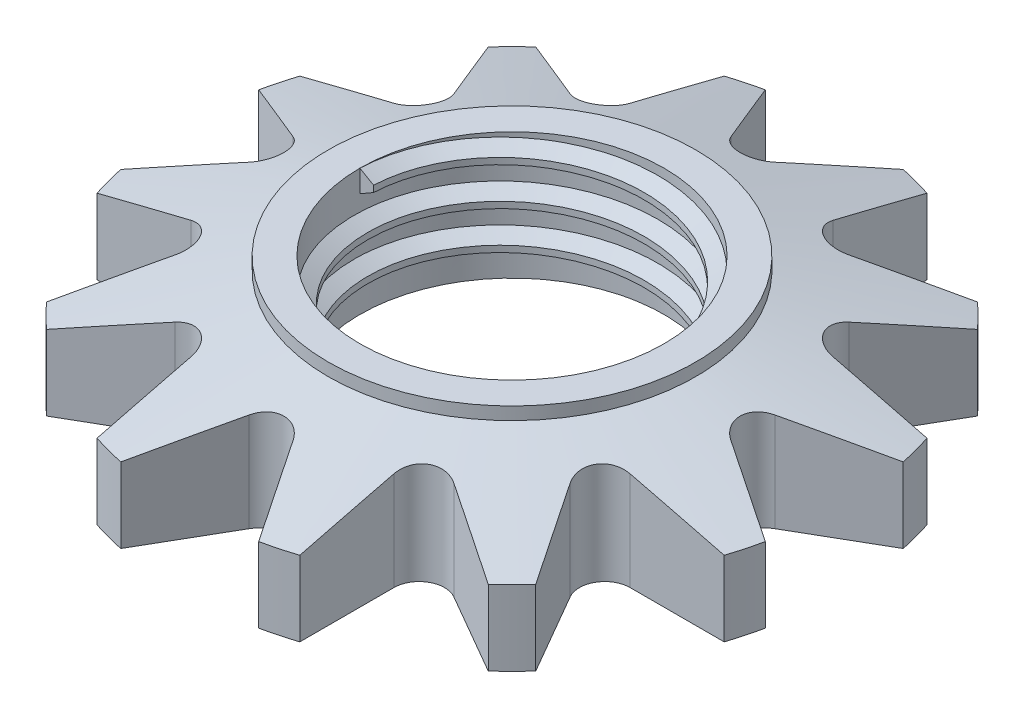
SolidWorks part; units mm, degrees
ref_plane "Front Plane" through (0, 0, 0) normal (0, 0, 1) x (1, 0, 0)
ref_plane "Top Plane" through (0, 0, 0) normal (0, 1, 0) x (1, 0, 0)
ref_plane "Right Plane" through (0, 0, 0) normal (1, 0, 0) x (0, 0, -1)
sketch "Sketch1" plane through (0, 0, 0) normal (0, 1, 0) x (1, 0, 0)
  circle A0 centre (0, 0) radius 26
  circle A1 centre (0, 0) radius 12
  dimension "D1" = 52
  dimension "D2" = 24
extrude "Boss-Extrude1" add sketch "Sketch1" along normal blind 9
sketch "Sketch2" plane through (0, 9, 0) normal (0, 1, 0) x (1, 0, 0)
  circle A0 centre (0, 0) radius 14.5
  circle A1 centre (0, 0) radius 12 construction
  circle A2 centre (0, 0) radius 12
  dimension "D1" = 29
extrude "Boss-Extrude2" add sketch "Sketch2" along normal blind 1
sketch "Sketch3" plane through (0, 9, 0) normal (0, 1, 0) x (1, 0, 0)
  line L0 (0, 26) -> (0, 0) construction
  line L1 (0, 0) -> (-26, 0) construction
  line L2 (-5.4411, 25.4243) -> (-1.7321, 19)
  line L3 (5.4411, 25.4243) -> (1.7321, 19)
  line L4 (8, 24.7386) -> (8, 17.3205)
  line L5 (17.4243, 19.2975) -> (11, 15.5885)
  line L6 (19.2975, 17.4243) -> (15.5885, 11)
  line L7 (24.7386, 8) -> (17.3205, 8)
  line L8 (25.4243, 5.4411) -> (19, 1.7321)
  line L9 (25.4243, -5.4411) -> (19, -1.7321)
  line L10 (24.7386, -8) -> (17.3205, -8)
  line L11 (19.2975, -17.4243) -> (15.5885, -11)
  line L12 (17.4243, -19.2975) -> (11, -15.5885)
  line L13 (8, -24.7386) -> (8, -17.3205)
  line L14 (5.4411, -25.4243) -> (1.7321, -19)
  line L15 (-5.4411, -25.4243) -> (-1.7321, -19)
  line L16 (-8, -24.7386) -> (-8, -17.3205)
  line L17 (-17.4243, -19.2975) -> (-11, -15.5885)
  line L18 (-19.2975, -17.4243) -> (-15.5885, -11)
  line L19 (-24.7386, -8) -> (-17.3205, -8)
  line L20 (-25.4243, -5.4411) -> (-19, -1.7321)
  line L21 (-25.4243, 5.4411) -> (-19, 1.7321)
  line L22 (-24.7386, 8) -> (-17.3205, 8)
  line L23 (-19.2975, 17.4243) -> (-15.5885, 11)
  line L24 (-17.4243, 19.2975) -> (-11, 15.5885)
  line L25 (-8, 24.7386) -> (-8, 17.3205)
  circle A0 centre (0, 0) radius 26 construction
  arc A1 (-1.7321, 19) -> (1.7321, 19) centre (0, 20) ccw
  arc A2 (5.4411, 25.4243) -> (-5.4411, 25.4243) centre (0, 0) ccw
  arc A3 (17.4243, 19.2975) -> (8, 24.7386) centre (0, 0) ccw
  arc A4 (8, 17.3205) -> (11, 15.5885) centre (10, 17.3205) ccw
  arc A5 (24.7386, 8) -> (19.2975, 17.4243) centre (0, 0) ccw
  arc A6 (15.5885, 11) -> (17.3205, 8) centre (17.3205, 10) ccw
  arc A7 (25.4243, -5.4411) -> (25.4243, 5.4411) centre (0, 0) ccw
  arc A8 (19, 1.7321) -> (19, -1.7321) centre (20, 0) ccw
  arc A9 (19.2975, -17.4243) -> (24.7386, -8) centre (0, 0) ccw
  arc A10 (17.3205, -8) -> (15.5885, -11) centre (17.3205, -10) ccw
  arc A11 (8, -24.7386) -> (17.4243, -19.2975) centre (0, 0) ccw
  arc A12 (11, -15.5885) -> (8, -17.3205) centre (10, -17.3205) ccw
  arc A13 (-5.4411, -25.4243) -> (5.4411, -25.4243) centre (0, 0) ccw
  arc A14 (1.7321, -19) -> (-1.7321, -19) centre (0, -20) ccw
  arc A15 (-17.4243, -19.2975) -> (-8, -24.7386) centre (0, 0) ccw
  arc A16 (-8, -17.3205) -> (-11, -15.5885) centre (-10, -17.3205) ccw
  arc A17 (-24.7386, -8) -> (-19.2975, -17.4243) centre (0, 0) ccw
  arc A18 (-15.5885, -11) -> (-17.3205, -8) centre (-17.3205, -10) ccw
  arc A19 (-25.4243, 5.4411) -> (-25.4243, -5.4411) centre (0, 0) ccw
  arc A20 (-19, -1.7321) -> (-19, 1.7321) centre (-20, 0) ccw
  arc A21 (-19.2975, 17.4243) -> (-24.7386, 8) centre (0, 0) ccw
  arc A22 (-17.3205, 8) -> (-15.5885, 11) centre (-17.3205, 10) ccw
  arc A23 (-8, 24.7386) -> (-17.4243, 19.2975) centre (0, 0) ccw
  arc A24 (-11, 15.5885) -> (-8, 17.3205) centre (-10, 17.3205) ccw
  point P69 (0, 0)
  dimension "D1" = 2
  dimension "D2" = 60
  dimension "D3" = 20
  dimension "D4" = 12
extrude "Cut-Extrude1" cut sketch "Sketch3" against normal through all
sketch "Sketch4" plane through (0, 0, 0) normal (0, 0, 1) x (1, 0, 0)
  line L0 (14.5, 9) -> (26.9071, 5.6755)
  line L1 (17.4243, 9) -> (11, 9) construction
  line L2 (14.5, 9) -> (14.5, 10) construction
  line L3 (26.9071, 5.6755) -> (26.9071, 9)
  line L4 (26.9071, 9) -> (14.5, 9)
  line L5 (0, 0) -> (0, 15.8829) construction
  line L6 (-1.7321, 0) -> (1.7321, 0) construction
  dimension "D1" = 15
revolve "Cut-Revolve1" cut sketch "Sketch4" angle 360 about L5
thread "Thread1" pitch 2 method extrude profile "Thread Profile1" start angle 0, offset 0, length 8.4, pitch 3, diameter 24
ref_plane "Plane1" through (-12, 10, 0) normal (0, 0, 1) x (-1, 0, 0)
sketch "Thread Profile1" plane through (-12, 10, 0) normal (0, 0, 1) x (-1, 0, 0)
  line L0 (0, 0) -> (0, 2) construction
  line L11 (0, 0) -> (0, 1.75)
  line L12 (0, 1.75) -> (-1.0825, 1.125)
  line L13 (-1.0825, 1.125) -> (-1.0825, 0.625)
  line L15 (-1.0825, 0.625) -> (0, 0)
  line L17 (-1.0825, 0.875) -> (0, 0.875) construction
  point P2 (0, 0)
  dimension "Pitch" = 2
  dimension "Profile_Angle" = 60
  dimension "Profile_Land" = 0.5
  dimension "Profile_Height" = 1.0825
